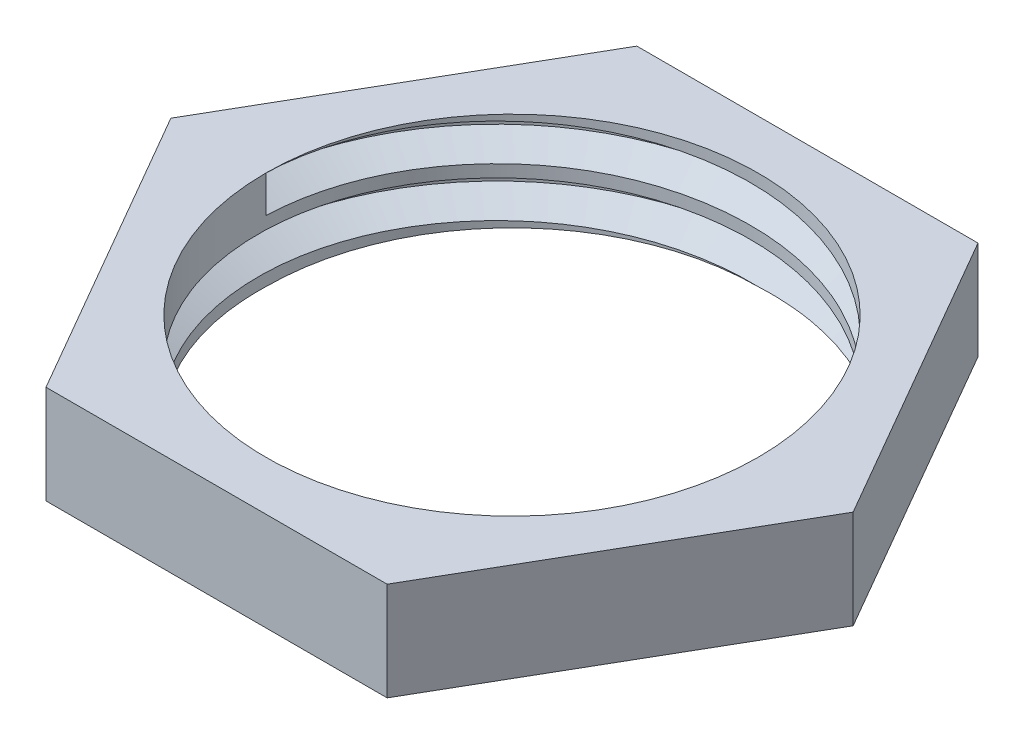
SolidWorks part; units mm, degrees
ref_plane "Front Plane" through (0, 0, 0) normal (0, 0, 1) x (1, 0, 0)
ref_plane "Top Plane" through (0, 0, 0) normal (0, 1, 0) x (1, 0, 0)
ref_plane "Right Plane" through (0, 0, 0) normal (1, 0, 0) x (0, 0, -1)
sketch "Sketch1" plane through (0, 0, 0) normal (0, 1, 0) x (1, 0, 0)
  line L1 (6.9282, 0) -> (3.4641, 6)
  line L2 (3.4641, 6) -> (-3.4641, 6)
  line L3 (-3.4641, 6) -> (-6.9282, 0)
  line L4 (-6.9282, 0) -> (-3.4641, -6)
  line L5 (-3.4641, -6) -> (3.4641, -6)
  line L6 (3.4641, -6) -> (6.9282, 0)
  circle A0 centre (0, 0) radius 6 construction
  circle A1 centre (0, 0) radius 5
extrude "Boss-Extrude1" add sketch "Sketch1" along normal blind 2
thread "Thread1" pitch 1 method cut profile "Thread Profile1" start angle 0, offset 0, length 2, pitch 1, diameter 10
ref_plane "Plane1" through (-5, 2, 0) normal (0, 0, 1) x (-1, 0, 0)
sketch "Thread Profile1" plane through (-5, 2, 0) normal (0, 0, 1) x (-1, 0, 0)
  line L0 (0, 0) -> (0, 1) construction
  line L1 (0, 0) -> (0.5413, 0.3125)
  line L2 (0.5413, 0.3125) -> (0.5413, 0.4375)
  line L3 (0.5413, 0.4375) -> (0, 0.75)
  line L4 (0.5413, 0.375) -> (0, 0.375) construction
  line L11 (0, 0) -> (0, 0.75)
  point P2 (0, 0)
  dimension "Pitch" = 1
  dimension "Profile_Angle" = 60
  dimension "Profile_Land" = 0.125
  dimension "Profile_Height" = 0.5413
